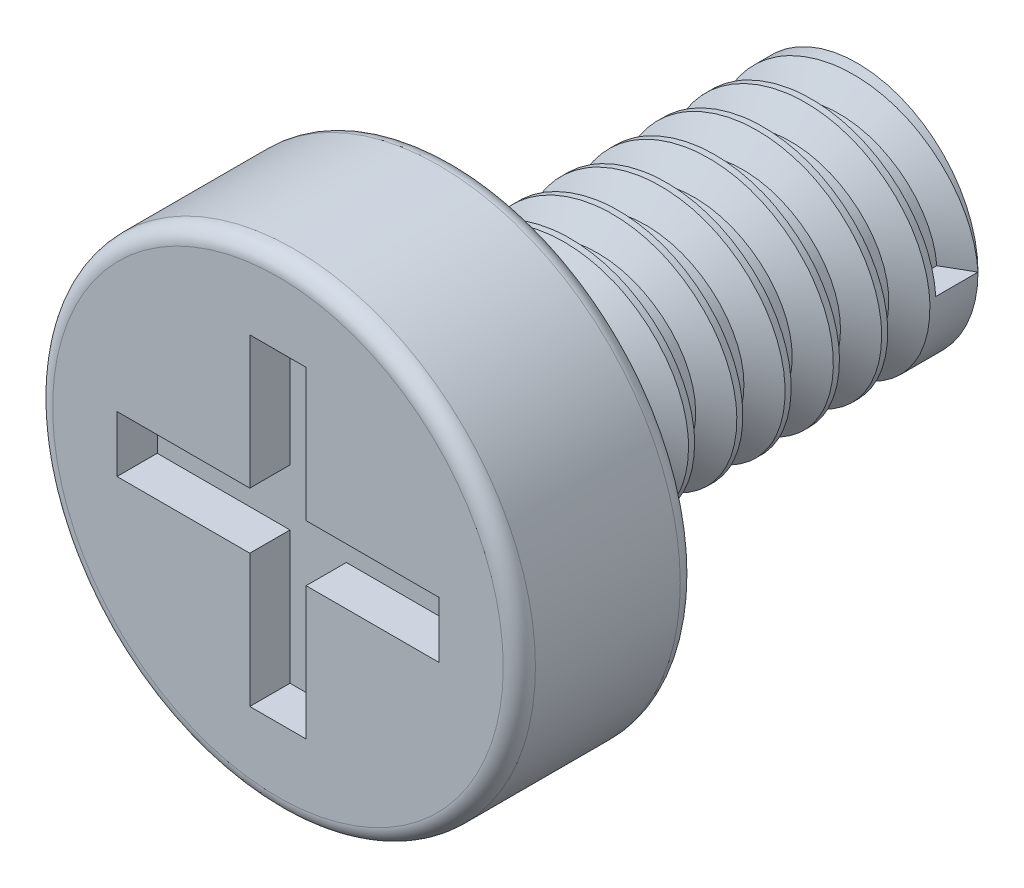
SolidWorks part; units mm, degrees
ref_plane "Front Plane" through (0, 0, 0) normal (0, 0, 1) x (1, 0, 0)
ref_plane "Top Plane" through (0, 0, 0) normal (0, 1, 0) x (1, 0, 0)
ref_plane "Right Plane" through (0, 0, 0) normal (1, 0, 0) x (0, 0, -1)
sketch "Sketch1" plane through (0, 0, 0) normal (0, 0, 1) x (1, 0, 0)
  circle A0 centre (0, 0) radius 1.5
  dimension "D1" = 3
extrude "Boss-Extrude1" add sketch "Sketch1" along normal blind 5
sketch "Sketch2" plane through (0, 0, 5) normal (0, 0, 1) x (1, 0, 0)
  circle A0 centre (0, 0) radius 3
  dimension "D1" = 6
extrude "Boss-Extrude2" add sketch "Sketch2" along normal blind 2.2
sketch "Sketch7" plane through (0, 0, 7.2) normal (0, 0, 1) x (1, 0, 0)
  line L1 (0.35, 2) -> (-0.35, 2)
  line L2 (0.35, 2) -> (0.35, -2)
  line L3 (0.35, -2) -> (-0.35, -2)
  line L4 (-0.35, 2) -> (-0.35, -2)
  line L5 (0, -2) -> (0, 2) construction
  line L6 (0.35, 0) -> (-0.35, 0) construction
  line L7 (2, -0.35) -> (-2, -0.35)
  line L8 (2, -0.35) -> (2, 0.35)
  line L9 (2, 0.35) -> (-2, 0.35)
  line L10 (-2, -0.35) -> (-2, 0.35)
  line L11 (0, 0.35) -> (0, -0.35) construction
  line L12 (2, 0) -> (-2, 0) construction
  point P0 (0, 0)
  point P4 (0, 0)
  dimension "D1" = 4
  dimension "D2" = 0.7
extrude "Cut-Extrude1" cut sketch "Sketch7" against normal blind 0.5 contours L9 L2 L1 L4 | L8 L9 L2 L7 | L2 L7 L4 L3 | L10 L7 L4 L9 | L2 L9 L4 L7 region at (0, 1.175, 7.2) region at (1.175, 0, 7.2) region at (0, 0, 7.2) region at (-1.175, 0, 7.2) region at (0, -1.175, 7.2)
fillet "Fillet1" radius 0.2 2 edges at (3, 0, 7.2) (3, 0, 5)
thread "Thread1" pitch 0.6 method cut profile "Thread Profile1" start angle 0, offset 0, length 0, pitch 0.6, diameter 3
ref_plane "Plane1" through (1.5, 0, 0) normal (0, -1, 0) x (1, 0, 0)
sketch "Thread Profile1" plane through (1.5, 0, 0) normal (0, -1, 0) x (1, 0, 0)
  line L0 (0, 0) -> (0, 0.6) construction
  line L11 (0, 0) -> (0, 0.525)
  line L12 (0, 0.525) -> (-0.3248, 0.3375)
  line L13 (-0.3248, 0.3375) -> (-0.3248, 0.1875)
  line L15 (-0.3248, 0.1875) -> (0, 0)
  line L17 (-0.3248, 0.2625) -> (0, 0.2625) construction
  point P2 (0, 0)
  dimension "Pitch" = 0.6
  dimension "Profile_Angle" = 60
  dimension "Profile_Land" = 0.15
  dimension "Profile_Height" = 0.3248
